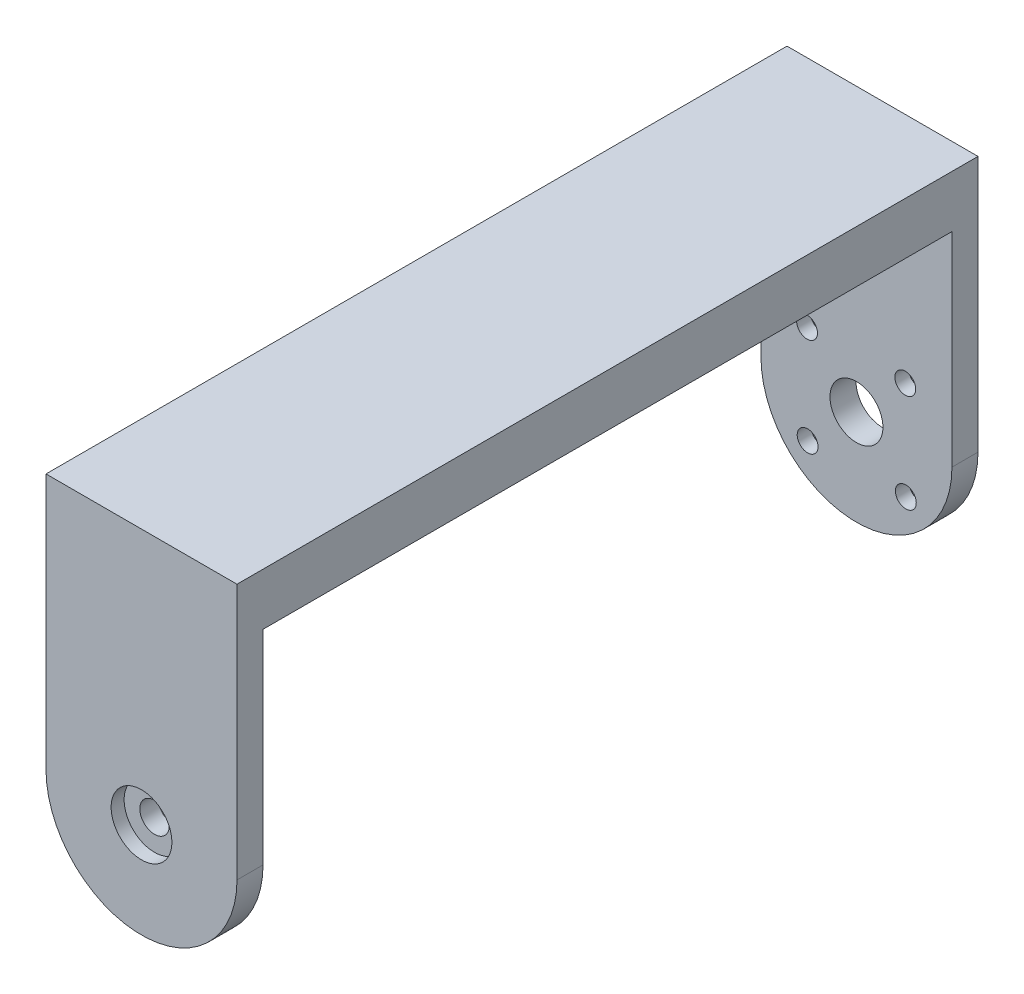
SolidWorks part; units mm, degrees
ref_plane "Plano frontal" through (0, 0, 0) normal (0, 0, 1) x (1, 0, 0)
ref_plane "Plano superior" through (0, 0, 0) normal (0, 1, 0) x (1, 0, 0)
ref_plane "Plano direito" through (0, 0, 0) normal (1, 0, 0) x (0, 0, -1)
sketch "Esboço1" plane through (0, 0, 0) normal (0, 0, 1) x (1, 0, 0)
  line L0 (11, -1.4281) -> (11, 25.0719)
  line L1 (11, 25.0719) -> (-11, 25.0719)
  line L2 (-11, 25.0719) -> (-11, -1.4281)
  line L4 (11, -3.4281) -> (11, 5.0719) construction
  line L5 (7.3, 10.0719) -> (-7.3, 10.0719) construction
  circle A3 centre (0, -1.4281) radius 11 construction
  arc A8 (-11, -1.4281) -> (11, -1.4281) centre (0, -1.4281) ccw
  circle A9 centre (0, -1.4281) radius 3.05 construction
  circle A10 centre (0, -1.4281) radius 3.05
  dimension "D1" = 15
extrude "Ressalto-extrusão1" add sketch "Esboço1" against normal blind 3
sketch "Esboço2" plane through (0, 25.0719, 0) normal (0, 1, 0) x (1, 0, 0)
  line L0 (-3.85, -78.5) -> (3.85, -78.5) construction
  line L1 (-11, 3) -> (11, 3)
  line L2 (-11, 3) -> (-11, -79.35)
  line L3 (-11, -79.35) -> (11, -79.35)
  line L4 (11, 3) -> (11, -79.35)
  dimension "D1" = 0.85
extrude "Ressalto-extrusão2" add sketch "Esboço2" along normal blind 3
sketch "Esboço3" plane through (0, 0, 79.35) normal (0, 0, 1) x (1, 0, 0)
  line L0 (11, 28.0719) -> (-11, 28.0719)
  line L1 (-11, 28.0719) -> (-11, -1.4281)
  line L2 (11, -1.4281) -> (11, 28.0719)
  arc A0 (-11, -1.4281) -> (11, -1.4281) centre (0, -1.4281) ccw
  circle A3 centre (0, -1.4281) radius 4 construction
extrude "Ressalto-extrusão3" add sketch "Esboço3" along normal blind 3
sketch "Esboço6" plane through (11, 0, 0) normal (1, 0, 0) x (0, 0, -1)
  line L0 (3, -1.4281) -> (3, 28.0719) construction
  line L1 (-82.35, 28.0719) -> (3, 28.0719)
  line L2 (-82.35, 28.0719) -> (-82.35, 22.0719)
  line L3 (-82.35, 22.0719) -> (3, 22.0719)
  line L4 (3, 28.0719) -> (3, 22.0719)
  line L5 (-79.35, 25.0719) -> (0, 25.0719) construction
  dimension "D1" = 3
extrude "Ressalto-extrusão5" add sketch "Esboço6" against normal blind 3
mirror "Espelhar1" about plane through (0, 0, 0) normal (1, 0, 0) of "Ressalto-extrusão5"
sketch "Esboço7" plane through (0, 0, 79.35) normal (0, 0, -1) x (-1, 0, 0)
  circle A0 centre (0, -1.4281) radius 2.75
  circle A2 centre (0, -1.4281) radius 3.25 construction
  dimension "D1" = 0.5
extrude "Ressalto-extrusão6" add sketch "Esboço7" along normal offset from surface (0.6 mm away) 0.25
hole_wizard "Rebaixo para parafuso com cabeça panela de M31" positions "Esboço8" profile "Esboço9" counterbore size "M3" standard "DIN" end condition up to next
sketch "Esboço8" plane through (0, 0, 82.35) normal (0, 0, 1) x (1, 0, 0)
  circle A0 centre (0, -1.4281) radius 3.25 construction
  point P0 (0, -1.4281)
  point P4 (0, 0)
sketch "Esboço9" plane through (0, -1.4281, 82.35) normal (1, 0, 0) x (0, -1, 0)
  line L0 (0, 0) -> (0, 3.6)
  line L1 (0, 3.6) -> (1.7, 3.6)
  line L3 (1.7, 3.6) -> (1.7, 1.5)
  line L4 (1.7, 1.5) -> (3.5, 1.5)
  line L5 (3.5, 1.5) -> (3.5, 0)
  line L7 (3.5, 0) -> (0, 0)
  line L11 (0, -6.35) -> (0, 107.95) construction
  dimension "Thru Hole Dia." = 3.4
  dimension "Thru Hole Depth" = 3.6
  dimension "C'Bore Dia." = 7
  dimension "C'Bore Depth" = 1.5
hole_wizard "Rebaixo para parafuso com cabeça redonda de M21" positions "Esboço10" profile "Esboço11" counterbore size "M2" standard "DIN" end condition up to next
sketch "Esboço10" plane through (0, 0, -3) normal (0, 0, -1) x (-1, 0, 0)
  circle A0 centre (-5.6247, 4.2606) radius 1.025 construction
  point P0 (-5.6247, 4.2606)
  point P3 (0, 0)
sketch "Esboço11" plane through (5.6247, 4.2606, -3) normal (1, 0, 0) x (0, 1, 0)
  line L0 (0, 0) -> (0, 3)
  line L1 (0, 3) -> (1.2, 3)
  line L3 (1.2, 3) -> (1.2, 1.4)
  line L4 (1.2, 1.4) -> (2.2, 1.4)
  line L5 (2.2, 1.4) -> (2.2, 0)
  line L7 (2.2, 0) -> (0, 0)
  line L11 (0, -6.35) -> (0, 107.95) construction
  dimension "Thru Hole Dia." = 2.4
  dimension "Thru Hole Depth" = 3
  dimension "C'Bore Dia." = 4.4
  dimension "C'Bore Depth" = 1.4
pattern_circular "PadrãoCircular1" count 4 over 360 about axis through (0, -1.4281, -3) along (0, 0, 1) of "Rebaixo para parafuso com cabeça redonda de M21"
